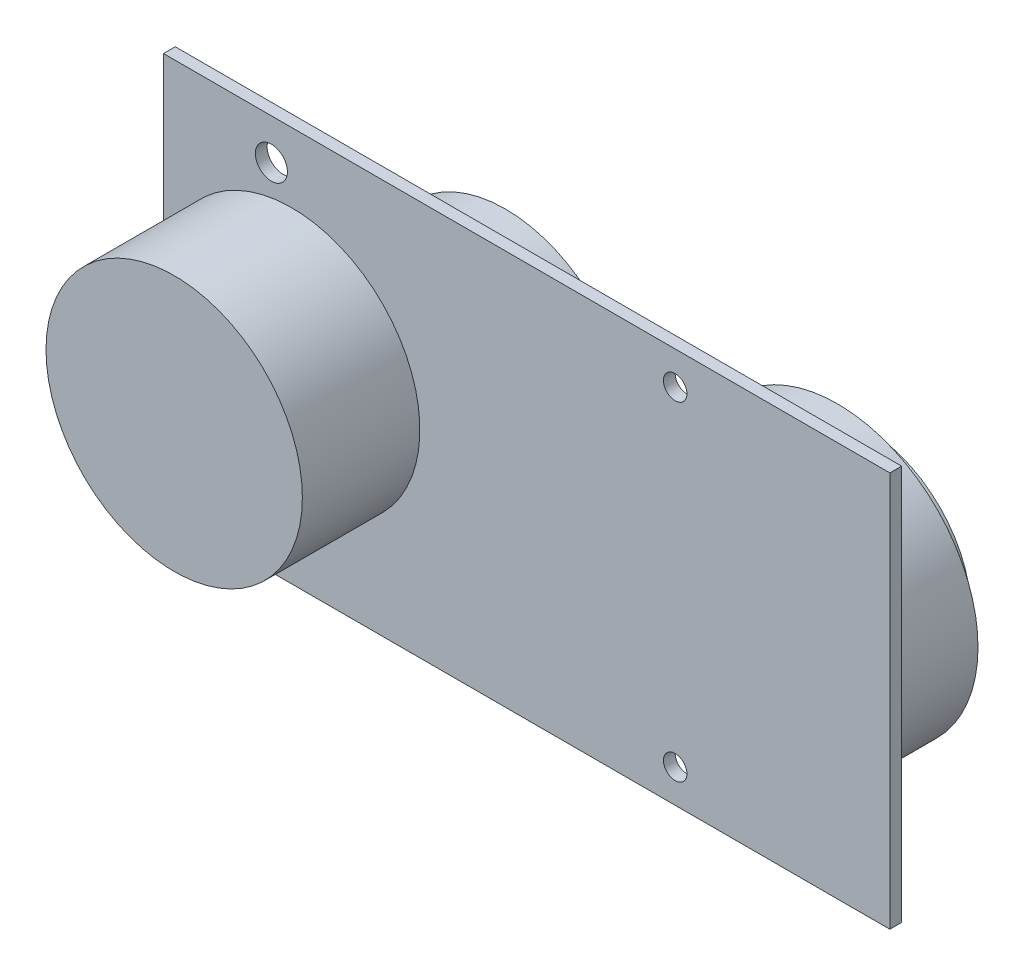
SolidWorks part; units mm, degrees
ref_plane "前视基准面" through (0, 0, 0) normal (0, 0, 1) x (1, 0, 0)
ref_plane "上视基准面" through (0, 0, 0) normal (0, 1, 0) x (1, 0, 0)
ref_plane "右视基准面" through (0, 0, 0) normal (1, 0, 0) x (0, 0, -1)
other "Configuration Table"
sketch "草图1" plane through (0, 0, 0) normal (0, 0, 1) x (1, 0, 0)
  circle A1 centre (0, 0) radius 12
  dimension "D2" = 24
extrude "凸台-拉伸1" add sketch "草图1" along normal blind 11 contours A1
sketch "草图2" plane through (0, 0, 0) normal (0, 0, -1) x (-1, 0, 0)
  circle A0 centre (0, 0) radius 3
  dimension "D1" = 6
extrude "凸台-拉伸2" add sketch "草图2" along normal blind 20 from surface starting at face at (12, 0, 11)
sketch "草图3" plane through (0, 0, 0) normal (0, 0, 1) x (1, 0, 0)
  line L0 (-12, 0) -> (0, 0) construction
  line L1 (-12, 18.5) -> (56, 18.5)
  line L2 (-12, 18.5) -> (-12, -18.5)
  line L3 (-12, -18.5) -> (56, -18.5)
  line L4 (56, 18.5) -> (56, -18.5)
  circle A0 centre (0, 0) radius 12 construction
  circle A1 centre (42.6, 0) radius 13.15
  dimension "D2" = 26.3
  dimension "D3" = 42.6
  dimension "D1" = 68
  dimension "D4" = 37
extrude "凸台-拉伸3" add sketch "草图3" against normal blind 1.1 contours L1 L4 L3 L2
extrude "凸台-拉伸4" add sketch "草图3<3>" against normal blind 11 contours A1
sketch "草图3<3>" plane through (0, 0, 0) normal (0, 0, 1) x (1, 0, 0) same geometry as "草图3"
sketch "草图5" plane through (0, 0, -11) normal (0, 0, -1) x (-1, 0, 0)
  circle A0 centre (-42.6, 0) radius 10
  circle A1 centre (-42.6, 0) radius 13.15 construction
  circle A2 centre (-42.6, 0) radius 13.15
  dimension "D1" = 20
extrude "切除-拉伸2" cut sketch "草图5" against normal blind 2.5
sketch "草图6" plane through (0, 0, -1.1) normal (0, 0, -1) x (-1, 0, 0)
  circle A0 centre (-13.5, 3.6) radius 11.8
  circle A1 centre (-26.7, -2.2) radius 13.5
  circle A2 centre (-26.7, -2.2) radius 3.05
  dimension "D1" = 23.6
  dimension "D4" = 27
  dimension "D7" = 6.1
  dimension "D2" = 13.5
  dimension "D3" = 3.6
  dimension "D5" = 26.7
  dimension "D6" = 2.2
extrude "凸台-拉伸5" add sketch "草图6" along normal blind 6.5 from surface contours A0 starting at face at (14.6667, 0, 0)
extrude "凸台-拉伸6" add sketch "草图6<3>" along normal blind 4.2 from surface contours A1 starting at face at (14.6667, 0, 0)
sketch "草图6<3>" plane through (0, 0, -1.1) normal (0, 0, -1) x (-1, 0, 0) same geometry as "草图6"
extrude "凸台-拉伸7" add sketch "草图6<4>" along normal blind 8.8 from surface contours A2 starting at face at (14.6667, 0, 0)
sketch "草图6<4>" plane through (0, 0, -1.1) normal (0, 0, -1) x (-1, 0, 0) same geometry as "草图6"
sketch "草图4" plane through (0, 0, -1.1) normal (0, 0, -1) x (-1, 0, 0)
  line L0 (1.9, -14.7) -> (1.9, 14.7) construction
  line L1 (1.9, 0) -> (0, 0) construction
  line L2 (-35.9, 15.4) -> (-35.9, -15.4) construction
  line L3 (-35.9, 0) -> (-42.6, 0) construction
  circle A0 centre (1.9, 14.7) radius 1.5
  circle A1 centre (1.9, -14.7) radius 1.5
  circle A2 centre (-35.9, 15.4) radius 1.1
  circle A3 centre (-35.9, -15.4) radius 1.1
  circle A4 centre (-42.6, 0) radius 1.6585
  dimension "D1" = 3
  dimension "D4" = 2.2
  dimension "D2" = 29.4
  dimension "D3" = 1.9
  dimension "D5" = 6.7
  dimension "D6" = 0.7
extrude "切除-拉伸1" cut sketch "草图4" against normal through all contours A3 | A2 | A0 | A1
sketch "草图7" plane through (0, 0, -11) normal (0, 0, -1) x (-1, 0, 0)
  line L0 (-48.85, 0) -> (-36.35, 0)
  circle A0 centre (-48.85, 0) radius 1.25
  circle A1 centre (-36.35, 0) radius 1.25
  circle A2 centre (-42.6, 0) radius 3.5304
  circle A3 centre (-42.6, 0) radius 10 construction
  dimension "D1" = 2.5
  dimension "D2" = 12.5
extrude "切除-拉伸3" cut sketch "草图7" against normal up to surface (2.5 mm away) contours A0 | A1 up to face at (42.6736, 0.0102, -8.5)
